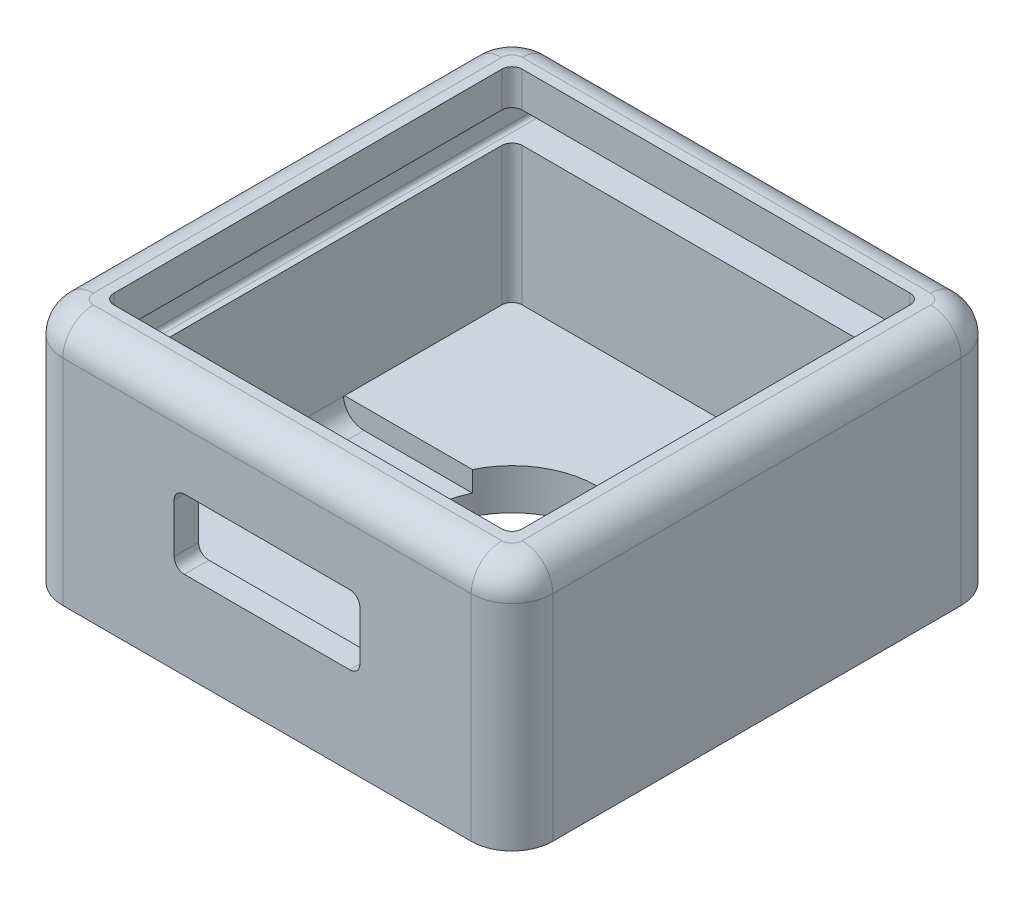
SolidWorks part; units mm, degrees
ref_plane "Front Plane" through (0, 0, 0) normal (0, 0, 1) x (1, 0, 0)
ref_plane "Top Plane" through (0, 0, 0) normal (0, 1, 0) x (1, 0, 0)
ref_plane "Right Plane" through (0, 0, 0) normal (1, 0, 0) x (0, 0, -1)
sketch "Sketch2" plane through (0, 0, 0) normal (0, 1, 0) x (1, 0, 0)
  line L1 (-10, -12) -> (10, -12)
  line L2 (-12, -10) -> (-12, 10)
  line L3 (-10, 12) -> (10, 12)
  line L4 (12, -10) -> (12, 10)
  line L5 (-12, -12) -> (12, 12) construction
  line L6 (-12, 12) -> (12, -12) construction
  arc A0 (-10, -12) -> (-12, -10) centre (-10, -10) cw
  arc A1 (10, -12) -> (12, -10) centre (10, -10) ccw
  arc A2 (10, 12) -> (12, 10) centre (10, 10) cw
  arc A3 (-12, 10) -> (-10, 12) centre (-10, 10) cw
  point P0 (0, 0)
  dimension "D3" = 2
  dimension "D1" = 24
  dimension "D2" = 24
extrude "Boss-Extrude2" add sketch "Sketch2" along normal blind 2
sketch "Sketch3" plane through (0, 2, 0) normal (0, 1, 0) x (1, 0, 0)
  line L1 (-9.5, -10) -> (9.5, -10)
  line L2 (-10, -9.5) -> (-10, 9.5)
  line L3 (-9.5, 10) -> (9.5, 10)
  line L4 (10, -9.5) -> (10, 9.5)
  line L5 (-10, -10) -> (10, 10) construction
  line L6 (-10, 10) -> (10, -10) construction
  line L7 (-10, -12) -> (10, -12)
  line L8 (-12, -10) -> (-12, 10)
  line L9 (-10, 12) -> (10, 12)
  line L10 (12, -10) -> (12, 10)
  line L11 (-12, -12) -> (12, 12) construction
  line L12 (-12, 12) -> (12, -12) construction
  arc A0 (9.5, -10) -> (10, -9.5) centre (9.5, -9.5) ccw
  arc A1 (-9.5, -10) -> (-10, -9.5) centre (-9.5, -9.5) cw
  arc A2 (9.5, 10) -> (10, 9.5) centre (9.5, 9.5) cw
  arc A3 (-10, 9.5) -> (-9.5, 10) centre (-9.5, 9.5) cw
  arc A4 (10, -12) -> (12, -10) centre (10, -10) ccw
  arc A5 (-10, -12) -> (-12, -10) centre (-10, -10) cw
  arc A6 (10, 12) -> (12, 10) centre (10, 10) cw
  arc A7 (-12, 10) -> (-10, 12) centre (-10, 10) cw
  point P0 (0, 0)
  point P18 (0, 0)
  dimension "D3" = 0.5
  dimension "D6" = 2
  dimension "D1" = 20
  dimension "D2" = 20
  dimension "D4" = 24
  dimension "D5" = 24
extrude "Boss-Extrude3" add sketch "Sketch3" along normal blind 10 contours A7 L9 A6 L10 A4 L7 A5 L8 | A3 L2 A1 L1 A0 L4 A2 L3
sketch "Sketch4" plane through (0, 0, 12) normal (0, 0, 1) x (1, 0, 0)
  line L0 (0, 0) -> (0, 12) construction
  line L1 (-4.05, 7.7) -> (4.05, 7.7)
  line L2 (-4.55, 7.2) -> (-4.55, 4.8)
  line L3 (-4.05, 4.3) -> (4.05, 4.3)
  line L4 (4.55, 7.2) -> (4.55, 4.8)
  line L5 (-4.55, 7.7) -> (4.55, 4.3) construction
  line L6 (-4.55, 4.3) -> (4.55, 7.7) construction
  line L7 (-10, 0) -> (10, 0) construction
  line L8 (-10, 12) -> (10, 12) construction
  arc A0 (-4.55, 4.8) -> (-4.05, 4.3) centre (-4.05, 4.8) ccw
  arc A1 (4.05, 4.3) -> (4.55, 4.8) centre (4.05, 4.8) ccw
  arc A2 (4.05, 7.7) -> (4.55, 7.2) centre (4.05, 7.2) cw
  arc A3 (-4.05, 7.7) -> (-4.55, 7.2) centre (-4.05, 7.2) ccw
  point P0 (0, 6)
  point P24 (0, 6)
  dimension "D3" = 0.5
  dimension "D1" = 9.1
  dimension "D2" = 3.4
extrude "Cut-Extrude1" cut sketch "Sketch4" against normal up to next contours L2 A0 L3 A1 L4 A2 L1 A3
sketch "Sketch5" plane through (0, 2, 0) normal (0, 1, 0) x (1, 0, 0)
  circle A0 centre (0, 0) radius 4.15
  dimension "D1" = 8.3
extrude "Cut-Extrude2" cut sketch "Sketch5" against normal up to next
sketch "Sketch6" plane through (0, 2, 0) normal (0, 1, 0) x (1, 0, 0)
  line L0 (-10, 0) -> (10, 0) construction
  line L1 (-10, -9.5) -> (-10, 9.5) construction
  line L2 (10, -9.5) -> (10, 9.5) construction
  line L4 (-10.0543, 1.8) -> (9.9457, 1.8)
  line L5 (-10.0543, 1.8) -> (-10.0543, -1.8)
  line L6 (-10.0543, -1.8) -> (9.9457, -1.8)
  line L7 (9.9457, 1.8) -> (9.9457, -1.8)
  line L8 (-10.0543, 1.8) -> (9.9457, -1.8) construction
  line L9 (-10.0543, -1.8) -> (9.9457, 1.8) construction
  point P6 (-0.0543, 0)
  dimension "D1" = 3.6
  dimension "D2" = 20
extrude "Cut-Extrude3" cut sketch "Sketch6" against normal blind 1
fillet "Fillet1" radius 1 2 edges at (9.9457, 1, 0) (-10.0543, 1, 0)
sketch "Sketch7" plane through (0, 0, 10) normal (0, 0, -1) x (-1, 0, 0)
  line L0 (4.05, 4.3) -> (-4.05, 4.3) construction
  line L1 (-6.05, 3.3) -> (6.05, 3.3)
  line L2 (-6.05, 3.3) -> (-6.05, 4.3)
  line L3 (-6.05, 4.3) -> (6.05, 4.3)
  line L4 (6.05, 3.3) -> (6.05, 4.3)
  line L5 (-6.05, 3.3) -> (6.05, 4.3) construction
  line L6 (-6.05, 4.3) -> (6.05, 3.3) construction
  line L7 (0, 4.3) -> (0, 2) construction
  line L8 (9.5, 2) -> (-9.5, 2) construction
  line L10 (-6.05, 8.26) -> (6.05, 8.26)
  line L11 (-6.05, 8.26) -> (-6.05, 4.3)
  line L12 (-6.05, 4.3) -> (6.05, 4.3)
  line L13 (6.05, 8.26) -> (6.05, 4.3)
  line L14 (-6.05, 8.26) -> (6.05, 4.3) construction
  line L15 (-6.05, 4.3) -> (6.05, 8.26) construction
  line L16 (4.05, 7.7) -> (-4.05, 7.7) construction
  point P0 (0, 3.8)
  point P12 (0, 6.28)
  line M10 (4.55, 7.2) -> (4.55, 4.8)
  arc M11 (4.55, 4.8) -> (4.05, 4.3) centre (4.05, 4.8) cw
  line M12 (4.05, 4.3) -> (-4.05, 4.3)
  arc M13 (-4.05, 4.3) -> (-4.55, 4.8) centre (-4.05, 4.8) cw
  line M14 (-4.55, 4.8) -> (-4.55, 7.2)
  arc M15 (-4.55, 7.2) -> (-4.05, 7.7) centre (-4.05, 7.2) cw
  line M16 (-4.05, 7.7) -> (4.05, 7.7)
  arc M17 (4.05, 7.7) -> (4.55, 7.2) centre (4.05, 7.2) cw
  dimension "D1" = 1
  dimension "D2" = 12.1
  dimension "D3" = 0.56
extrude "Cut-Extrude4" cut sketch "Sketch7" against normal blind 0.8 contours L13 L10 L11 L3 M13 M14 M15 M16 M17 M10 M11 | L1 L4 L3 L2 M12 region at (0, 3.8, 10) region at (5.9227, 6.28, 10)
sketch "Sketch8" plane through (0, 2, 0) normal (0, 1, 0) x (1, 0, 0)
  line L0 (0, -10) -> (0, 10) construction
  line L1 (-6.7, -4.15) -> (6.7, -4.15)
  line L2 (-6.7, -4.15) -> (-6.7, -5.3232)
  line L3 (-6.7, -5.3232) -> (6.7, -5.3232)
  line L4 (6.7, -4.15) -> (6.7, -5.3232)
  line L5 (-6.7, -4.15) -> (6.7, -5.3232) construction
  line L6 (-6.7, -5.3232) -> (6.7, -4.15) construction
  line L7 (-9.5, -10) -> (9.5, -10) construction
  line L8 (-9.5, 10) -> (9.5, 10) construction
  arc A0 (-3.7393, -1.8) -> (3.7393, -1.8) centre (0, 0) ccw construction
  point P0 (0, -4.7366)
  dimension "D1" = 13.4
extrude "Boss-Extrude4" add sketch "Sketch8" along normal blind 1.3
sketch "Sketch10" plane through (0, 3.3, 0) normal (0, 1, 0) x (1, 0, 0)
  line L0 (6.7, -5.3232) -> (6.01, -5.3232)
  line L1 (-6.7, -4.15) -> (-6.01, -4.15)
  line L2 (-6.7, -4.15) -> (-6.7, -5.3232)
  line L3 (-6.7, -5.3232) -> (-6.01, -5.3232)
  line L4 (-6.01, -4.15) -> (-6.01, -5.3232)
  line L5 (-6.7, -4.15) -> (-6.01, -5.3232) construction
  line L6 (-6.7, -5.3232) -> (-6.01, -4.15) construction
  line L7 (-6.7, -5.3232) -> (6.7, -5.3232) construction
  line L8 (-6.7, -4.15) -> (-6.7, -5.3232) construction
  line L9 (6.7, -4.15) -> (-6.7, -4.15) construction
  line L10 (0, -4.15) -> (0, -5.3232) construction
  line L11 (6.01, -4.15) -> (6.01, -5.3232)
  line L12 (6.7, -4.15) -> (6.01, -4.15)
  line L13 (6.7, -4.15) -> (6.7, -5.3232)
  point P0 (-6.355, -4.7366)
  dimension "D1" = 0.69
extrude "Boss-Extrude5" add sketch "Sketch10" along normal blind 2
fillet "Fillet2" radius 0.5 2 edges at (6.01, 3.3, 4.7366) (-6.01, 3.3, 4.7366)
fillet "Fillet6" radius 0.5 2 edges at (6.7, 2, 4.7366) (-6.7, 2, 4.7366)
sketch "Sketch13" [suppressed] plane through (0, 0, 0) normal (0, 0, 1) x (1, 0, 0)
  line L2 (-12, 12) -> (-12, 13)
  line L3 (-10, 12) -> (-10, 2) construction
  line L4 (-12, 12) -> (-12, 0) construction
  line L5 (-11, 14) -> (-9, 14)
  line L6 (-9, 14) -> (-9, 13)
  line L8 (-10, 12) -> (-9, 12)
  line L9 (-12, 12) -> (-12, 11.5)
  line L10 (-12, 11.5) -> (-9, 11.5)
  line L11 (-9, 12) -> (-9, 11.5)
  arc A0 (-12, 13) -> (-11, 14) centre (-11, 13) cw
  spline S0 degree 3 poles (-10, 12) (-10, 12.2913) (-9.9111, 12.6573) (-9.459, 13.006) (-9, 13) knots 0 0 0 0 0.483993 1 1 1 1
  point P14 (-12, 14)
  point P15 (0, 11.75)
  dimension "D2" = 1
  dimension "D1" = 2
  dimension "D3" = 1
  dimension "D4" = 0.5
  dimension "D5" = 1
fillet "Fillet8" radius 1.5 8 edges at (-11.4142, 12, -11.4142) (-12, 12, 0) (-11.4142, 12, 11.4142) (0, 12, 12) (11.4142, 12, 11.4142) (12, 12, 0) (11.4142, 12, -11.4142) (0, 12, -12)
sketch "Sketch21" plane through (0, 0, -12) normal (0, 0, -1) x (-1, 0, 0)
  line L0 (0, 10.5) -> (0, 0) construction
  line L1 (-10.3, 10.2666) -> (10.3, 10.2666)
  line L2 (-10.5, 10.0666) -> (-10.5, 8.9666)
  line L3 (-10.3, 8.7666) -> (10.3, 8.7666)
  line L4 (10.5, 10.0666) -> (10.5, 8.9666)
  line L5 (-10.5, 10.2666) -> (10.5, 8.7666) construction
  line L6 (-10.5, 8.7666) -> (10.5, 10.2666) construction
  line L7 (10, 10.5) -> (-10, 10.5) construction
  arc A0 (10.3, 8.7666) -> (10.5, 8.9666) centre (10.3, 8.9666) ccw
  arc A1 (10.3, 10.2666) -> (10.5, 10.0666) centre (10.3, 10.0666) cw
  arc A2 (-10.5, 8.9666) -> (-10.3, 8.7666) centre (-10.3, 8.9666) ccw
  arc A3 (-10.3, 10.2666) -> (-10.5, 10.0666) centre (-10.3, 10.0666) ccw
  point P0 (0, 9.5166)
  dimension "D2" = 0.2
  dimension "D1" = 21
  dimension "D3" = 1.5
extrude "Cut-Extrude6" cut sketch "Sketch21" against normal blind 22.5
fillet "Fillet9" radius 0.2 8 edges at (10.4414, 8.8252, 10.5) (10.5, 9.5166, 10.5) (10.4414, 10.208, 10.5) (0, 10.2666, 10.5) (-10.4414, 10.208, 10.5) (-10.5, 9.5166, 10.5) (-10.4414, 8.8252, 10.5) (0, 8.7666, 10.5)
